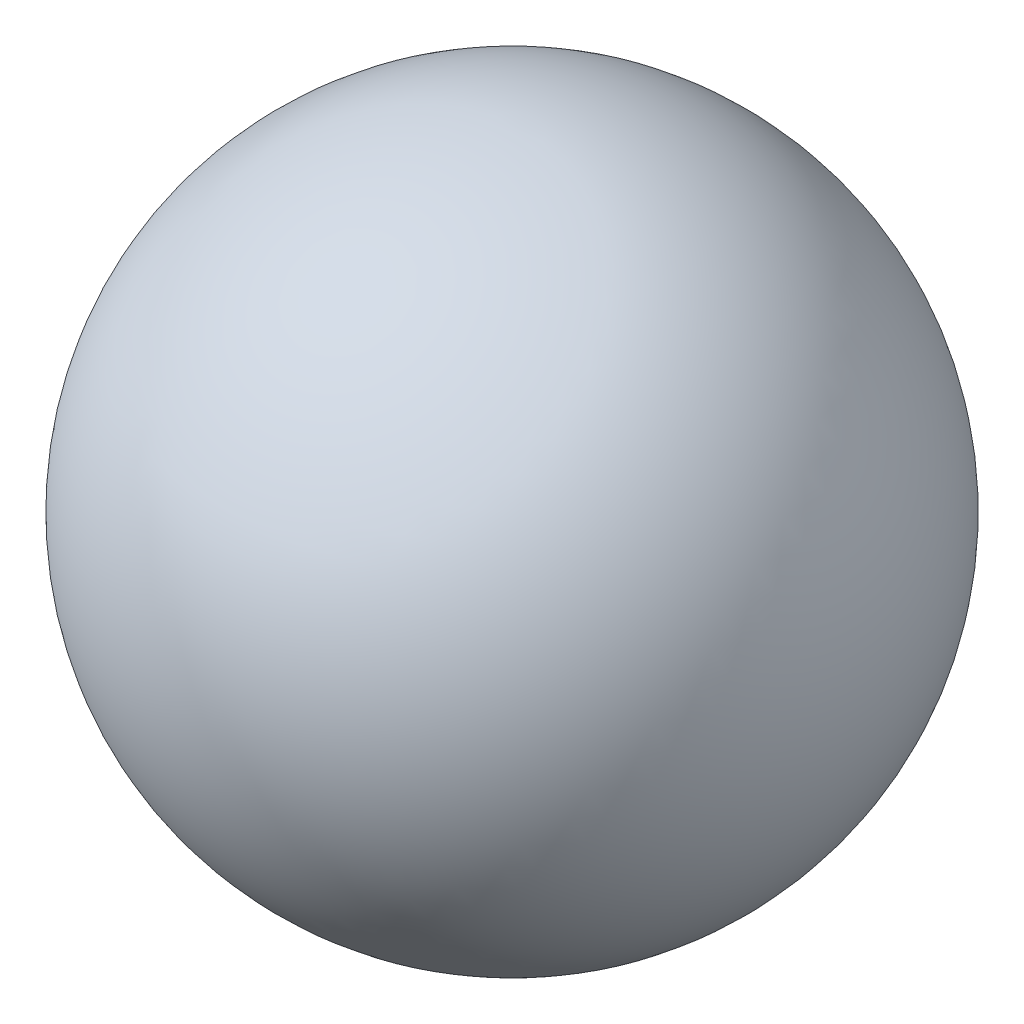
SolidWorks part; units mm, degrees
material "Epoxy, Unfilled"
ref_plane "Front Plane" through (0, 0, 0) normal (0, 0, 1) x (1, 0, 0)
ref_plane "Top Plane" through (0, 0, 0) normal (0, 1, 0) x (1, 0, 0)
ref_plane "Right Plane" through (0, 0, 0) normal (1, 0, 0) x (0, 0, -1)
sketch "Sketch1" plane through (0, 0, 0) normal (0, 0, 1) x (1, 0, 0)
  line L0 (0, 319.61) -> (0, 310)
  line L1 (0, -310) -> (0, -319.61)
  arc A0 (0, 310) -> (0, -310) centre (0, 0) ccw
  arc A1 (0, 319.61) -> (0, -319.61) centre (0, 0) ccw
revolve "Revolve1" add sketch "Sketch1" angle 360 about L0
